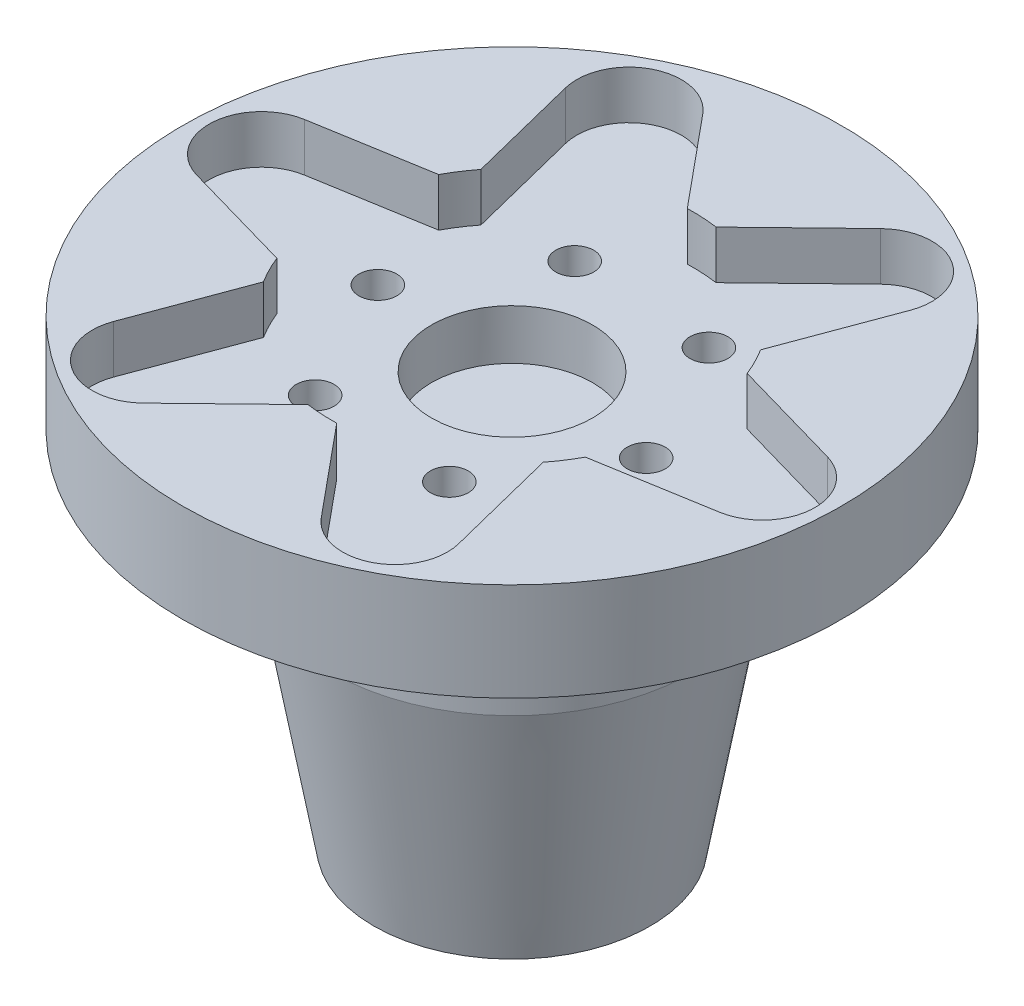
SolidWorks part; units mm, degrees
material "PVC 0.007 Plasticized"
ref_plane "Front Plane" through (0, 0, 0) normal (0, 0, 1) x (1, 0, 0)
ref_plane "Top Plane" through (0, 0, 0) normal (0, 1, 0) x (1, 0, 0)
ref_plane "Right Plane" through (0, 0, 0) normal (1, 0, 0) x (0, 0, -1)
sketch "Sketch1" plane through (0, 325.3674, 0) normal (0, 1, 0) x (1, 0, 0)
  line L0 (-14.7362, -1.885) -> (-7.6933, -3.8933)
  line L1 (-7.6933, -3.8933) -> (-10.246, -10.7577)
  line L2 (-5.7357, -13.7044) -> (-0.4749, -8.6093)
  line L3 (-0.4749, -8.6093) -> (4.1934, -14.2521)
  line L4 (9.0005, -11.8194) -> (7.2184, -4.716)
  line L5 (7.2184, -4.716) -> (14.4394, -3.4945)
  line L6 (14.7362, 1.885) -> (7.6933, 3.8933)
  line L7 (7.6933, 3.8933) -> (10.246, 10.7577)
  line L8 (5.7357, 13.7044) -> (0.4749, 8.6093)
  line L9 (0.4749, 8.6093) -> (-4.1934, 14.2521)
  line L10 (-9.0005, 11.8194) -> (-7.2184, 4.716)
  line L11 (-7.2184, 4.716) -> (-14.4394, 3.4945)
  line L12 (6.2658, 13.157) -> (0.4131, 7.4886)
  line L13 (0.4131, 7.4886) -> (-4.7805, 13.7664)
  line L14 (-8.2614, 12.0049) -> (-6.2788, 4.1021)
  line L15 (-6.2788, 4.1021) -> (-14.3123, 2.7431)
  line L16 (-14.5272, -1.1522) -> (-6.6919, -3.3865)
  line L17 (-6.6919, -3.3865) -> (-9.5318, -11.0233)
  line L18 (-6.2658, -13.157) -> (-0.4131, -7.4886)
  line L19 (-0.4131, -7.4886) -> (4.7805, -13.7664)
  line L20 (8.2614, -12.0049) -> (6.2788, -4.1021)
  line L21 (6.2788, -4.1021) -> (14.3123, -2.7431)
  line L22 (14.5272, 1.1522) -> (6.6919, 3.3865)
  line L23 (6.6919, 3.3865) -> (9.5318, 11.0233)
  line L24 (6.2658, 13.157) -> (0.4131, 7.4886)
  line L25 (0.4131, 7.4886) -> (-4.7805, 13.7664)
  line L26 (-8.2614, 12.0049) -> (-6.2788, 4.1021)
  line L27 (-6.2788, 4.1021) -> (-14.3123, 2.7431)
  line L28 (-14.5272, -1.1522) -> (-6.6919, -3.3865)
  line L29 (-6.6919, -3.3865) -> (-9.5318, -11.0233)
  line L30 (-6.2658, -13.157) -> (-0.4131, -7.4886)
  line L31 (-0.4131, -7.4886) -> (4.7805, -13.7664)
  line L32 (8.2614, -12.0049) -> (6.2788, -4.1021)
  line L33 (6.2788, -4.1021) -> (14.3123, -2.7431)
  line L34 (14.5272, 1.1522) -> (6.6919, 3.3865)
  line L35 (6.6919, 3.3865) -> (9.5318, 11.0233)
  circle A0 centre (0, 0) radius 9.525 construction
  circle A1 centre (0, 0) radius 9.525
  circle A2 centre (0, 0) radius 17.3753 construction
  circle A3 centre (0, 0) radius 17.3753
  arc A4 (-10.246, -10.7577) -> (-5.7357, -13.7044) centre (-7.6572, -11.7204) ccw
  arc A5 (4.1934, -14.2521) -> (9.0005, -11.8194) centre (6.3215, -12.4915) ccw
  arc A6 (-4.7805, 13.7664) -> (-8.2614, 12.0049) centre (-6.3215, 12.4915) ccw
  arc A7 (-14.3123, 2.7431) -> (-14.5272, -1.1522) centre (-13.9787, 0.7712) ccw
  arc A8 (-9.5318, -11.0233) -> (-6.2658, -13.157) centre (-7.6572, -11.7204) ccw
  arc A9 (4.7805, -13.7664) -> (8.2614, -12.0049) centre (6.3215, -12.4915) ccw
  arc A10 (14.3123, -2.7431) -> (14.5272, 1.1522) centre (13.9787, -0.7712) ccw
  arc A11 (9.5318, 11.0233) -> (6.2658, 13.157) centre (7.6572, 11.7204) ccw
  arc A12 (-4.7805, 13.7664) -> (-8.2614, 12.0049) centre (-6.3215, 12.4915) ccw
  arc A13 (-14.3123, 2.7431) -> (-14.5272, -1.1522) centre (-13.9787, 0.7712) ccw
  arc A14 (-9.5318, -11.0233) -> (-6.2658, -13.157) centre (-7.6572, -11.7204) ccw
  arc A15 (4.7805, -13.7664) -> (8.2614, -12.0049) centre (6.3215, -12.4915) ccw
  arc A16 (14.3123, -2.7431) -> (14.5272, 1.1522) centre (13.9787, -0.7712) ccw
  arc A17 (9.5318, 11.0233) -> (6.2658, 13.157) centre (7.6572, 11.7204) ccw
  arc A18 (14.4394, -3.4945) -> (14.7362, 1.885) centre (13.9787, -0.7712) ccw
  arc A19 (10.246, 10.7577) -> (5.7357, 13.7044) centre (7.6572, 11.7204) ccw
  arc A20 (-4.1934, 14.2521) -> (-9.0005, 11.8194) centre (-6.3215, 12.4915) ccw
  arc A21 (-14.4394, 3.4945) -> (-14.7362, -1.885) centre (-13.9787, 0.7712) ccw
  circle A22 centre (-4.1021, -6.2788) radius 1 construction
  circle A23 centre (3.3865, -6.6919) radius 1 construction
  circle A24 centre (7.4886, -0.4131) radius 1 construction
  circle A25 centre (4.1021, 6.2788) radius 1 construction
  circle A26 centre (-3.3865, 6.6919) radius 1 construction
  circle A27 centre (-7.4886, 0.4131) radius 1 construction
  circle A28 centre (-4.1021, -6.2788) radius 1
  circle A29 centre (3.3865, -6.6919) radius 1
  circle A30 centre (7.4886, -0.4131) radius 1
  circle A31 centre (4.1021, 6.2788) radius 1
  circle A32 centre (-3.3865, 6.6919) radius 1
  circle A33 centre (-7.4886, 0.4131) radius 1
  line M21 (6.2658, 13.157) -> (0.4131, 7.4886)
  line M22 (0.4131, 7.4886) -> (-4.7805, 13.7664)
  arc M23 (-4.7805, 13.7664) -> (-8.2614, 12.0049) centre (-6.3215, 12.4915) ccw
  line M24 (-8.2614, 12.0049) -> (-6.2788, 4.1021)
  line M25 (-6.2788, 4.1021) -> (-14.3123, 2.7431)
  arc M26 (-14.3123, 2.7431) -> (-14.5272, -1.1522) centre (-13.9787, 0.7712) ccw
  line M27 (-14.5272, -1.1522) -> (-6.6919, -3.3865)
  line M28 (-6.6919, -3.3865) -> (-9.5318, -11.0233)
  arc M29 (-9.5318, -11.0233) -> (-6.2658, -13.157) centre (-7.6572, -11.7204) ccw
  line M30 (-6.2658, -13.157) -> (-0.4131, -7.4886)
  line M31 (-0.4131, -7.4886) -> (4.7805, -13.7664)
  arc M32 (4.7805, -13.7664) -> (8.2614, -12.0049) centre (6.3215, -12.4915) ccw
  line M33 (8.2614, -12.0049) -> (6.2788, -4.1021)
  line M34 (6.2788, -4.1021) -> (14.3123, -2.7431)
  arc M35 (14.3123, -2.7431) -> (14.5272, 1.1522) centre (13.9787, -0.7712) ccw
  line M36 (14.5272, 1.1522) -> (6.6919, 3.3865)
  line M37 (6.6919, 3.3865) -> (9.5318, 11.0233)
  arc M38 (9.5318, 11.0233) -> (6.2658, 13.157) centre (7.6572, 11.7204) ccw
  circle M39 centre (0, 0) radius 4.25
  circle M40 centre (7.3837, 11.3018) radius 1
  circle M41 centre (5.7429, 8.7903) radius 1
  circle M42 centre (4.1021, 6.2788) radius 1
  circle M43 centre (-3.3865, 6.6919) radius 1
  circle M44 centre (-4.7411, 9.3686) radius 1
  circle M45 centre (-6.0958, 12.0454) radius 1
  circle M46 centre (-7.4886, 0.4131) radius 1
  circle M47 centre (-10.4841, 0.5784) radius 1
  circle M48 centre (-13.4795, 0.7436) radius 1
  circle M49 centre (-4.1021, -6.2788) radius 1
  circle M50 centre (-5.7429, -8.7903) radius 1
  circle M51 centre (-7.3837, -11.3018) radius 1
  circle M52 centre (3.3865, -6.6919) radius 1
  circle M53 centre (4.7411, -9.3686) radius 1
  circle M54 centre (6.0958, -12.0454) radius 1
  circle M55 centre (7.4886, -0.4131) radius 1
  circle M56 centre (10.4841, -0.5784) radius 1
  circle M57 centre (13.4795, -0.7436) radius 1
  dimension "D1" = 0
  dimension "D2" = 0.762
extrude "Boss-Extrude1" add sketch "Sketch1" against normal blind 2.54 contours A3 A21 L11 A1 L10 A20 L9 L8 A19 L7 L6 A18 L5 L4 A5 L3 L2 A4 L1 L0 region at (-16.8838, 325.3674, 0)
extrude "Boss-Extrude2" add sketch "Sketch1<3>" against normal up to surface (2.635 mm away) from surface contours A3 A21 L11 A1 L10 A20 L9 L8 A19 L7 L6 A18 L5 L4 A5 L3 L2 A4 L1 L0 | L3 A5 L4 A1 L31 M33 M32 | A1 L31 M32 M33 M53 M54 | A1 M53 | M54 | A1 L29 M29 M30 M50 M51 | L1 A4 L2 A1 L29 M30 M29 | M51 | A1 M50 | A1 L27 M26 M27 M47 M48 | L11 A21 L0 A1 L27 M27 M26 | A1 M47 | M48 | A1 L25 M23 M24 M44 M45 | L9 A20 L10 A1 L25 M24 M23 | M45 | A1 M44 | L7 A19 L8 A1 L35 M21 M38 | A1 L35 M38 M21 M41 M40 | A1 M41 | M40 | L5 A18 L6 A1 L33 M36 M35 | A1 L33 M35 M36 M56 M57 | A1 M56 | M57 | L2 A1 L3 | L3 A1 L30 L2 M31 | A1 M50 | A1 L32 L34 L24 L26 L28 L30 M31 M53 M34 M56 M37 M41 M22 M44 M25 M47 M28 M50 M39 M43 M49 M55 M52 M46 M42 | L0 A1 L1 | L28 A1 L0 L1 M28 | A1 M47 | L10 A1 L11 | L26 A1 L10 L11 M25 | L8 A1 L9 | L24 A1 L8 L9 M22 | A1 M44 | A1 M41 | L6 A1 L7 | L34 A1 L6 L7 M37 | A1 M56 | L4 A1 L5 | L32 A1 L4 L5 M34 | A1 M53 region at (-16.6204, 325.3674, -0.9169) region at (-8.9579, 325.3674, 3.1198) region at (-8.2235, 325.3674, 4.1616) region at (-9.1825, 325.3674, 1.1693) region at (-12.2411, 325.3674, -0.6753) region at (-7.9597, 325.3674, 5.4671) region at (-7.7158, 325.3674, -5.0409) region at (-7.7953, 325.3674, -4.5796) region at (-10.4863, 325.3674, -0.5785) region at (-9.5001, 325.3674, -0.5241) region at (-6.7054, 325.3674, 10.2635) region at (-8.1286, 325.3674, -8.8728) region at (-5.2039, 325.3674, 7.9653) region at (-5.7441, 325.3674, 8.7921) region at (-5.5357, 325.3674, -10.9388) region at (-1.777, 325.3674, 9.317) region at (-0.5077, 325.3674, 9.2025) region at (-4.7421, 325.3674, -9.3706) region at (-4.2962, 325.3674, -8.4894) region at (0.7546, 325.3674, 9.6242) region at (0.5077, 325.3674, -9.2025) region at (0.067, 325.3674, -9.0396) region at (5.5357, 325.3674, 10.9388) region at (3.6216, 325.3674, -11.474) region at (4.2962, 325.3674, 8.4894) region at (4.7421, 325.3674, 9.3706) region at (6.7054, 325.3674, -10.2635) region at (7.1816, 325.3674, 6.1986) region at (7.7158, 325.3674, 5.0409) region at (5.7441, 325.3674, -8.7921) region at (5.2039, 325.3674, -7.9653) region at (8.7008, 325.3674, 4.1533) region at (8.2235, 325.3674, -4.1616) region at (7.8627, 325.3674, -4.4615) region at (12.2411, 325.3674, 0.6753) region at (9.5001, 325.3674, 0.5241) region at (10.4863, 325.3674, 0.5785) region at (-16.8838, 325.3674, 0) region at (7.3837, 325.3674, -11.3018) region at (-6.0958, 325.3674, -12.0454) region at (-13.4795, 325.3674, -0.7436) region at (-7.3837, 325.3674, 11.3018) region at (6.0958, 325.3674, 12.0454) region at (13.4795, 325.3674, 0.7436) starting at face at (0, 322.8274, 0)
sketch "Sketch1<3>" plane through (0, 325.3674, 0) normal (0, 1, 0) x (1, 0, 0) same geometry as "Sketch1"
sketch "Sketch2" plane through (0, 320.1924, 0) normal (0, -1, 0) x (1, 0, 0)
  circle A0 centre (0, 0) radius 9.525
  dimension "D1" = 19.05
extrude "Boss-Extrude4" add sketch "Sketch2" along normal blind 19.05
chamfer "Chamfer1" distance 12.7 angle 10 1 edges at (0, 301.1424, -9.525) first distance on face at (0, 301.1424, -9.525)
